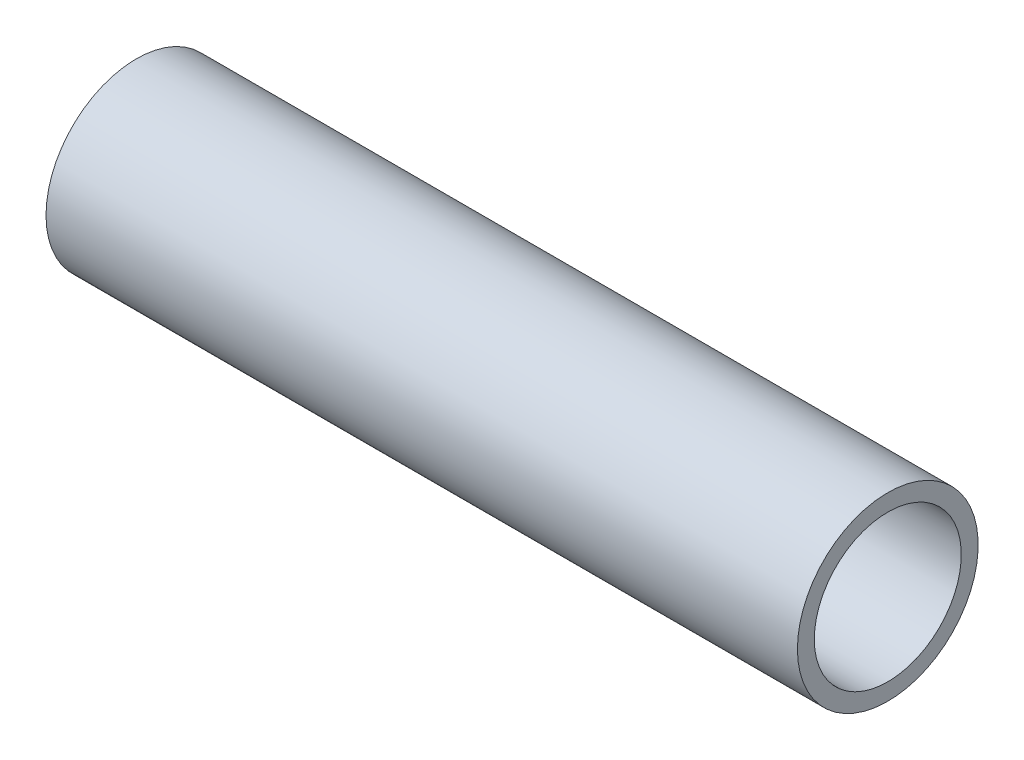
SolidWorks part; units mm, degrees
ref_plane "Front Plane" through (0, 0, 0) normal (0, 0, 1) x (1, 0, 0)
ref_plane "Top Plane" through (0, 0, 0) normal (0, 1, 0) x (1, 0, 0)
ref_plane "Right Plane" through (0, 0, 0) normal (1, 0, 0) x (0, 0, -1)
sketch "Tube_T6_Stub Sketch" plane through (0, 0, 0) normal (0, 0, 1) x (1, 0, 0)
  line L0 (-1000, 0) -> (1000, 0) construction
  line L1 (-19.8, 3.8735) -> (-19.8, 4.7625)
  line L2 (-19.8, 4.7625) -> (19.8, 4.7625)
  line L3 (19.8, 4.7625) -> (19.8, 3.8735)
  line L4 (19.8, 3.8735) -> (-19.8, 3.8735)
revolve "Tube_T6_Stub" add sketch "Tube_T6_Stub Sketch" angle 360 about L0
ref_axis "Engine Axis" through (21.78, 0, 0) along (-1, 0, 0)
